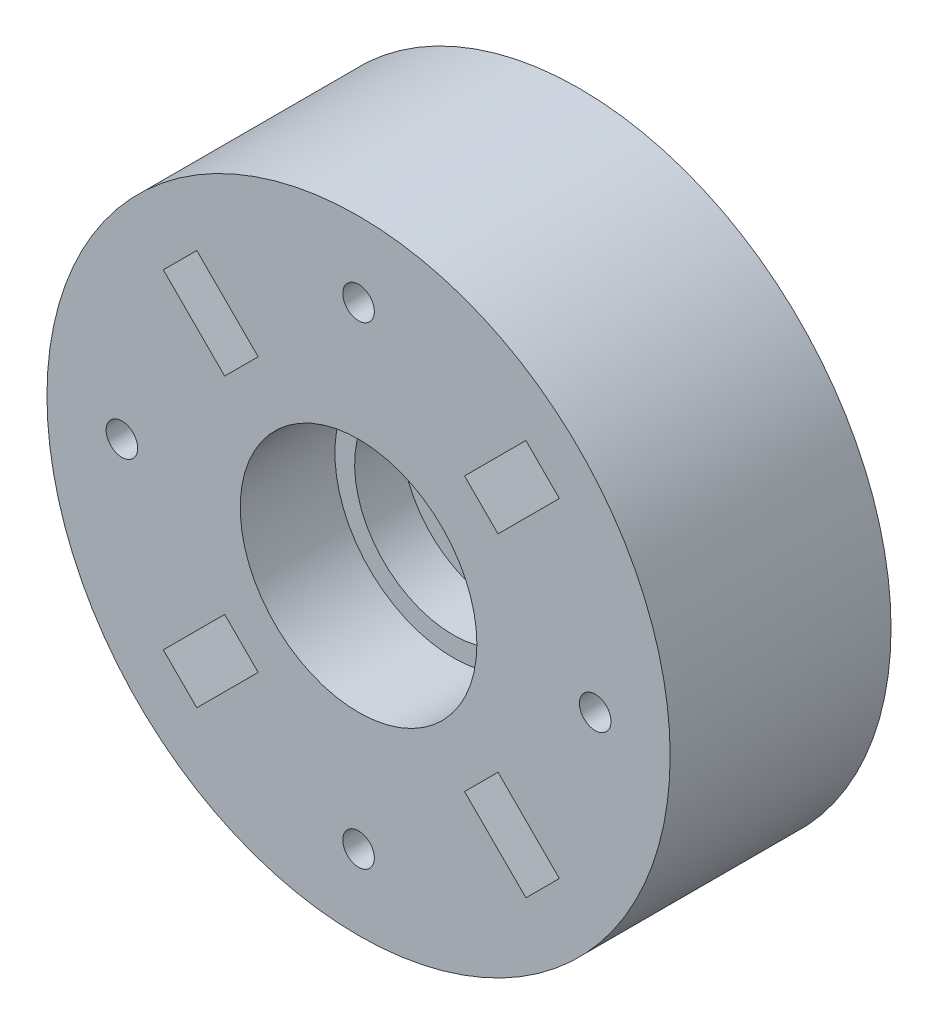
SolidWorks part; units mm, degrees
ref_plane "Alzado" through (0, 0, 0) normal (0, 0, 1) x (1, 0, 0)
ref_plane "Planta" through (0, 0, 0) normal (0, 1, 0) x (1, 0, 0)
ref_plane "Vista lateral" through (0, 0, 0) normal (1, 0, 0) x (0, 0, -1)
sketch "Croquis1" plane through (0, 0, 0) normal (0, 0, 1) x (1, 0, 0)
  line L0 (0, 50.6458) -> (0, -51.1293) construction
  circle A0 centre (0, 0) radius 39.5
  circle A1 centre (0, 0) radius 12.5
  circle A2 centre (0, 30) radius 2
  circle A3 centre (30, 0) radius 2
  circle A4 centre (0, -30) radius 2
  circle A5 centre (-30, 0) radius 2
  point P17 (0, 0)
  dimension "D1" = 79
  dimension "D2" = 25
  dimension "D4" = 4
  dimension "D3" = 30
  dimension "D5" = 4
extrude "Saliente-Extruir1" add sketch "Croquis1" along normal blind 28
sketch "Croquis3" plane through (0, 0, 28) normal (0, 0, 1) x (1, 0, 0)
  line L0 (0, 0) -> (28.2843, 28.2843) construction
  line L1 (0, 0) -> (39.5, 0) construction
  line L2 (17.6777, 13.435) -> (25.4558, 21.2132)
  line L3 (17.6777, 13.435) -> (13.435, 17.6777)
  line L4 (25.4558, 21.2132) -> (21.2132, 25.4558)
  line L5 (13.435, 17.6777) -> (21.2132, 25.4558)
  line L6 (17.6777, 13.435) -> (21.2132, 25.4558) construction
  line L7 (25.4558, 21.2132) -> (13.435, 17.6777) construction
  line L8 (13.435, -16.9706) -> (21.2132, -24.7487)
  line L9 (13.435, -16.9706) -> (17.6777, -12.7279)
  line L10 (17.6777, -12.7279) -> (25.4558, -20.5061)
  line L11 (21.2132, -24.7487) -> (25.4558, -20.5061)
  line L12 (-16.9706, -12.7279) -> (-24.7487, -20.5061)
  line L13 (-16.9706, -12.7279) -> (-12.7279, -16.9706)
  line L14 (-12.7279, -16.9706) -> (-20.5061, -24.7487)
  line L15 (-24.7487, -20.5061) -> (-20.5061, -24.7487)
  line L16 (-12.7279, 17.6777) -> (-20.5061, 25.4558)
  line L17 (-12.7279, 17.6777) -> (-16.9706, 13.435)
  line L18 (-16.9706, 13.435) -> (-24.7487, 21.2132)
  line L19 (-20.5061, 25.4558) -> (-24.7487, 21.2132)
  circle A0 centre (0, 0) radius 39.5 construction
  circle A1 centre (0, 0) radius 15
  point P8 (19.4454, 19.4454)
  point P27 (0.3536, 0.3536)
  dimension "D9" = 30
  dimension "D1" = 40
  dimension "D2" = 45
  dimension "D3" = 3
  dimension "D4" = 3
  dimension "D5" = 11
  dimension "D6" = 27.5
  dimension "D7" = 6
  dimension "D8" = 4
extrude "Cortar-Extruir1" cut sketch "Croquis3" against normal blind 12
sketch "Croquis5" plane through (0, 0, 0) normal (0, 0, -1) x (-1, 0, 0)
  circle A0 centre (0, 0) radius 16.8579
  dimension "D1" = 33.7158
extrude "Saliente-Extruir2" add sketch "Croquis5" against normal blind 10
sketch "Croquis4" plane through (0, 0, 0) normal (0, 0, -1) x (-1, 0, 0)
  line L0 (30, -3.5) -> (33.0311, -1.75)
  line L1 (3.5, 30) -> (1.75, 33.0311)
  line L2 (1.75, 33.0311) -> (-1.75, 33.0311)
  line L3 (-1.75, 33.0311) -> (-3.5, 30)
  line L4 (-3.5, 30) -> (-1.75, 26.9689)
  line L5 (-1.75, 26.9689) -> (1.75, 26.9689)
  line L6 (1.75, 26.9689) -> (3.5, 30)
  line L7 (33.0311, -1.75) -> (33.0311, 1.75)
  line L8 (33.0311, 1.75) -> (30, 3.5)
  line L9 (30, 3.5) -> (26.9689, 1.75)
  line L10 (26.9689, 1.75) -> (26.9689, -1.75)
  line L11 (26.9689, -1.75) -> (30, -3.5)
  line L12 (-3.5, -30) -> (-1.75, -33.0311)
  line L13 (-1.75, -33.0311) -> (1.75, -33.0311)
  line L14 (1.75, -33.0311) -> (3.5, -30)
  line L15 (3.5, -30) -> (1.75, -26.9689)
  line L16 (1.75, -26.9689) -> (-1.75, -26.9689)
  line L17 (-1.75, -26.9689) -> (-3.5, -30)
  line L18 (-30, 3.5) -> (-33.0311, 1.75)
  line L19 (-33.0311, 1.75) -> (-33.0311, -1.75)
  line L20 (-33.0311, -1.75) -> (-30, -3.5)
  line L21 (-30, -3.5) -> (-26.9689, -1.75)
  line L22 (-26.9689, -1.75) -> (-26.9689, 1.75)
  line L23 (-26.9689, 1.75) -> (-30, 3.5)
  line L24 (0, 0) -> (28.2843, 28.2843) construction
  line L25 (0, 0) -> (39.5, 0) construction
  line L26 (0.3536, -13.7886) -> (29.3449, 15.2028)
  line L27 (0.3536, -13.7886) -> (-13.7886, 0.3536)
  line L28 (29.3449, 15.2028) -> (15.2028, 29.3449)
  line L29 (-13.7886, 0.3536) -> (15.2028, 29.3449)
  line L30 (0.3536, -13.7886) -> (15.2028, 29.3449) construction
  line L31 (29.3449, 15.2028) -> (-13.7886, 0.3536) construction
  line L32 (25.1023, 25.1023) -> (18.7383, 31.4663) construction
  line L33 (25.1023, 25.1023) -> (28.9736, 21.231) construction
  line L34 (0, 0) -> (-15.8104, -15.8104) construction
  line L35 (-9.5459, -9.5459) -> (-4.5375, -14.5544) construction
  line L36 (-9.5459, -9.5459) -> (-14.3054, -4.7865) construction
  line L37 (21.9203, 28.2843) -> (-17.5609, -11.1969) construction
  line L38 (28.2843, 21.9203) -> (-9.2053, -15.5692) construction
  circle A0 centre (0, 30) radius 3.5 construction
  circle A1 centre (0, 0) radius 39.5 construction
  circle A3 centre (-12.7279, -6.364) radius 1.75
  circle A4 centre (-6.364, -12.7279) radius 1.75
  circle A5 centre (21.9203, 28.2843) radius 1.75
  circle A6 centre (28.2843, 21.9203) radius 1.75
  point P30 (0, 0)
  point P36 (7.7782, 7.7782)
  dimension "D11" = 3.5
  dimension "D12" = 3.5
  dimension "D13" = 3.5
  dimension "D14" = 3.5
  dimension "D1" = 4
  dimension "D2" = 40
  dimension "D3" = 45
  dimension "D4" = 20
  dimension "D5" = 10
  dimension "D6" = 9.5
  dimension "D7" = 4.5
  dimension "D8" = 4.5
  dimension "D9" = 4
  dimension "D10" = 4
  dimension "D15" = 41
extrude "Cortar-Extruir2" cut sketch "Croquis4" against normal blind 10
